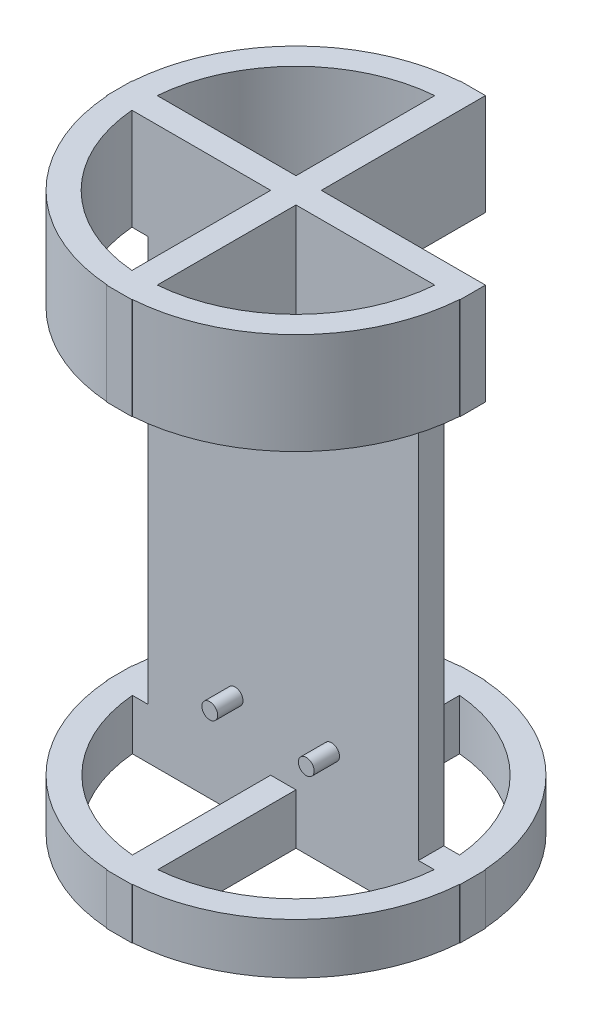
SolidWorks part; units mm, degrees
ref_plane "Front Plane" through (0, 0, 0) normal (0, 0, 1) x (1, 0, 0)
ref_plane "Top Plane" through (0, 0, 0) normal (0, 1, 0) x (1, 0, 0)
ref_plane "Right Plane" through (0, 0, 0) normal (1, 0, 0) x (0, 0, -1)
sketch "Sketch1" plane through (0, 0, 0) normal (0, 1, 0) x (1, 0, 0)
  line L0 (0, 34.9) -> (0, -34.9)
  line L1 (-34.9, 0) -> (34.9, 0)
  line L2 (0, 34.9) -> (34.9, 0)
  line L3 (34.9, 0) -> (0, -34.9)
  line L4 (-34.9, 0) -> (0, -34.9)
  line L5 (0, 34.9) -> (-34.9, 0)
  circle A0 centre (0, 0) radius 34.9
  dimension "D1" = 69.8
extrude "Extrude-Thin1" add sketch "Sketch1" along normal blind 10 thin contours A0 thin type one direction reverse wall 5
extrude "Extrude-Thin2" add sketch "Sketch1<3>" along normal blind 10 thin contours L0 | L1 thin type mid plane wall 5
sketch "Sketch1<3>" plane through (0, 0, 0) normal (0, 1, 0) x (1, 0, 0) same geometry as "Sketch1"
sketch "Sketch2" plane through (0, 10, 0) normal (0, 1, 0) x (1, 0, 0)
  line L0 (2.5, 2.5) -> (29.7953, 2.5) construction
  line L1 (-26.6714, -2.5) -> (26.6714, -2.5)
  line L2 (-26.6714, -2.5) -> (-26.6714, 2.5)
  line L3 (-26.6714, 2.5) -> (26.6714, 2.5)
  line L4 (26.6714, -2.5) -> (26.6714, 2.5)
  line L5 (-26.6714, -2.5) -> (26.6714, 2.5) construction
  line L6 (-26.6714, 2.5) -> (26.6714, -2.5) construction
  point P0 (0, 0)
  dimension "D1" = 53.3428
extrude "Boss-Extrude1" add sketch "Sketch2" along normal blind 80
sketch "Sketch3" plane through (0, 0, 2.5) normal (0, 0, 1) x (1, 0, 0)
  line L0 (0, 61.0073) -> (0, 18.9927)
  circle A0 centre (-9.525, 77.1246) radius 1.5621
  circle A1 centre (-9.525, 20) radius 1.5621
  circle A2 centre (9.525, 20) radius 1.5621
  circle A3 centre (9.525, 77.1246) radius 1.5621
  dimension "D1" = 3.1242
  dimension "D2" = 3.1242
  dimension "D3" = 9.525
  dimension "D4" = 9.525
  dimension "D5" = 57.1246
  dimension "D6" = 20
extrude "Boss-Extrude2" add sketch "Sketch3" along normal blind 5 contours A0 | A3 | A2 | A1
sketch "Sketch6" plane through (0, 90, 0) normal (0, 1, 0) x (1, 0, 0)
  line L0 (0, 34.9) -> (0, -34.9)
  line L1 (-34.9, 0) -> (34.9, 0)
  line L2 (20.9518, 21.4714) -> (24.374, 24.9784)
  circle A0 centre (0, 0) radius 34.9
  circle A1 centre (0, 0) radius 30
  dimension "D1" = 69.8
  dimension "D2" = 60
extrude "Boss-Extrude4" add sketch "Sketch6" along normal blind 20 separate body contours A1 L0 A0 L1 | A1 L1 A0 L0 | A1 L0 A0 L1 region at (-0.4936, 90, -32.45) region at (-32.45, 90, 0.4936) region at (24.329, 90, 24.329)
extrude "Extrude-Thin4" add sketch "Sketch6<6>" along normal blind 20 thin contours L1 | L0 thin type mid plane wall 5
sketch "Sketch6<6>" plane through (0, 90, 0) normal (0, 1, 0) x (1, 0, 0) same geometry as "Sketch6"
